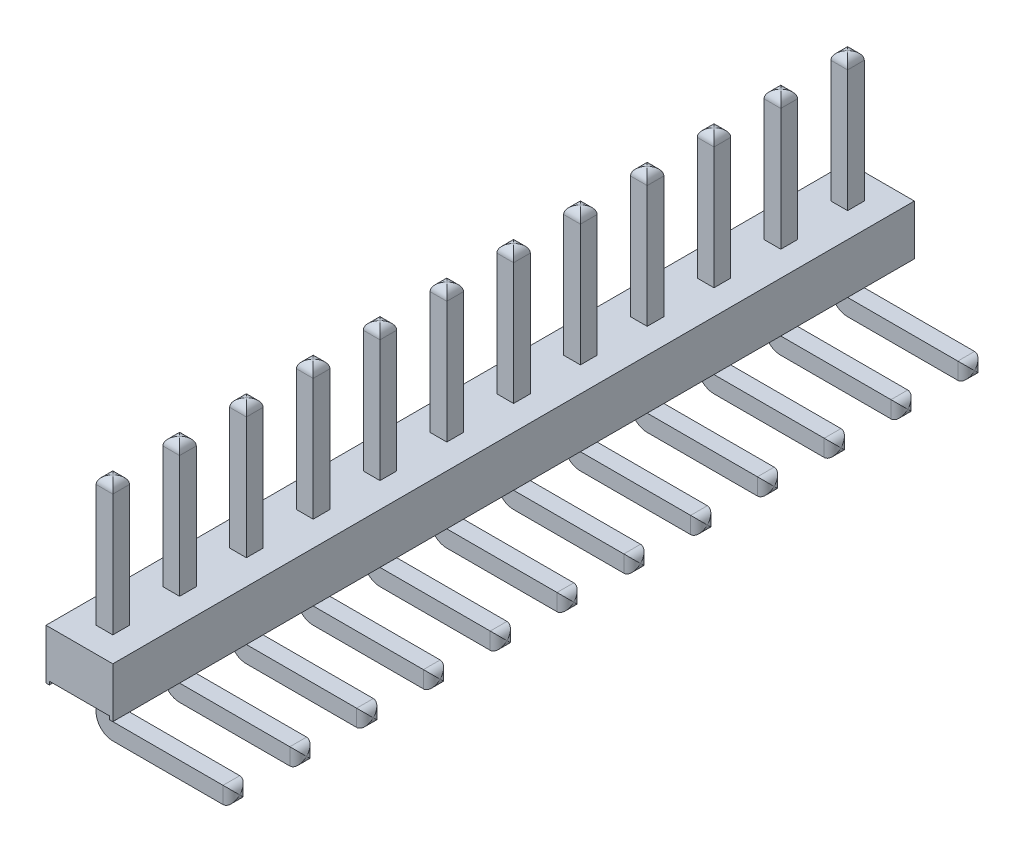
SolidWorks part; units mm, degrees
material "銅"
ref_plane "Front Plane" through (0, 0, 0) normal (0, 0, 1) x (1, 0, 0)
ref_plane "Top Plane" through (0, 0, 0) normal (0, 1, 0) x (1, 0, 0)
ref_plane "Right Plane" through (0, 0, 0) normal (1, 0, 0) x (0, 0, -1)
sketch "Sketch1" plane through (0, 0, 0) normal (0, 0, 1) x (1, 0, 0)
  line L0 (0.1, -1.5) -> (0.1, -1.3997)
  line L1 (0, 0) -> (2, 0)
  line L2 (0, 0) -> (0, -1.5)
  line L3 (0, -1.5) -> (0.1, -1.5)
  line L4 (2, 0) -> (2, -1.5)
  line L5 (0.1, -1.3997) -> (1.9019, -1.3997)
  line L6 (1.9019, -1.3997) -> (1.9019, -1.5)
  line L7 (1.9019, -1.5) -> (2, -1.5)
  dimension "D1" = 2
  dimension "D2" = 1.5
  dimension "D3" = 0.1
extrude "Boss-Extrude1" add sketch "Sketch1" against normal blind 24
sketch "Sketch2" plane through (0, 0, 0) normal (0, 1, 0) x (1, 0, 0)
  line L0 (1, 24) -> (1, 0) construction
  line L1 (2, 24) -> (0, 24) construction
  line L2 (2, 0) -> (0, 0) construction
  line L3 (1, 23.25) -> (0.75, 23.25)
  line L4 (0.75, 23.25) -> (0.75, 22.75)
  line L5 (0.75, 22.75) -> (1, 22.75)
  line L6 (1, 22.75) -> (1.25, 22.75)
  line L7 (1.25, 22.75) -> (1.25, 23.25)
  line L8 (1.25, 23.25) -> (1, 23.25)
  line L9 (0.75, 20.75) -> (1, 20.75)
  line L10 (0.75, 21.25) -> (0.75, 20.75)
  line L11 (1, 21.25) -> (0.75, 21.25)
  line L12 (1.25, 21.25) -> (1, 21.25)
  line L13 (1.25, 20.75) -> (1.25, 21.25)
  line L14 (1, 20.75) -> (1.25, 20.75)
  line L15 (0.75, 18.75) -> (1, 18.75)
  line L16 (0.75, 19.25) -> (0.75, 18.75)
  line L17 (1, 19.25) -> (0.75, 19.25)
  line L18 (1.25, 19.25) -> (1, 19.25)
  line L19 (1.25, 18.75) -> (1.25, 19.25)
  line L20 (1, 18.75) -> (1.25, 18.75)
  line L21 (0.75, 16.75) -> (1, 16.75)
  line L22 (0.75, 17.25) -> (0.75, 16.75)
  line L23 (1, 17.25) -> (0.75, 17.25)
  line L24 (1.25, 17.25) -> (1, 17.25)
  line L25 (1.25, 16.75) -> (1.25, 17.25)
  line L26 (1, 16.75) -> (1.25, 16.75)
  line L27 (0.75, 14.75) -> (1, 14.75)
  line L28 (0.75, 15.25) -> (0.75, 14.75)
  line L29 (1, 15.25) -> (0.75, 15.25)
  line L30 (1.25, 15.25) -> (1, 15.25)
  line L31 (1.25, 14.75) -> (1.25, 15.25)
  line L32 (1, 14.75) -> (1.25, 14.75)
  line L33 (0.75, 12.75) -> (1, 12.75)
  line L34 (0.75, 13.25) -> (0.75, 12.75)
  line L35 (1, 13.25) -> (0.75, 13.25)
  line L36 (1.25, 13.25) -> (1, 13.25)
  line L37 (1.25, 12.75) -> (1.25, 13.25)
  line L38 (1, 12.75) -> (1.25, 12.75)
  line L39 (0.75, 10.75) -> (1, 10.75)
  line L40 (0.75, 11.25) -> (0.75, 10.75)
  line L41 (1, 11.25) -> (0.75, 11.25)
  line L42 (1.25, 11.25) -> (1, 11.25)
  line L43 (1.25, 10.75) -> (1.25, 11.25)
  line L44 (1, 10.75) -> (1.25, 10.75)
  line L45 (0.75, 8.75) -> (1, 8.75)
  line L46 (0.75, 9.25) -> (0.75, 8.75)
  line L47 (1, 9.25) -> (0.75, 9.25)
  line L48 (1.25, 9.25) -> (1, 9.25)
  line L49 (1.25, 8.75) -> (1.25, 9.25)
  line L50 (1, 8.75) -> (1.25, 8.75)
  line L51 (0.75, 6.75) -> (1, 6.75)
  line L52 (0.75, 7.25) -> (0.75, 6.75)
  line L53 (1, 7.25) -> (0.75, 7.25)
  line L54 (1.25, 7.25) -> (1, 7.25)
  line L55 (1.25, 6.75) -> (1.25, 7.25)
  line L56 (1, 6.75) -> (1.25, 6.75)
  line L57 (0.75, 4.75) -> (1, 4.75)
  line L58 (0.75, 5.25) -> (0.75, 4.75)
  line L59 (1, 5.25) -> (0.75, 5.25)
  line L60 (1.25, 5.25) -> (1, 5.25)
  line L61 (1.25, 4.75) -> (1.25, 5.25)
  line L62 (1, 4.75) -> (1.25, 4.75)
  line L63 (0.75, 2.75) -> (1, 2.75)
  line L64 (0.75, 3.25) -> (0.75, 2.75)
  line L65 (1, 3.25) -> (0.75, 3.25)
  line L66 (1.25, 3.25) -> (1, 3.25)
  line L67 (1.25, 2.75) -> (1.25, 3.25)
  line L68 (1, 2.75) -> (1.25, 2.75)
  line L69 (0.75, 0.75) -> (1, 0.75)
  line L70 (0.75, 1.25) -> (0.75, 0.75)
  line L71 (1, 1.25) -> (0.75, 1.25)
  line L72 (1.25, 1.25) -> (1, 1.25)
  line L73 (1.25, 0.75) -> (1.25, 1.25)
  line L74 (1, 0.75) -> (1.25, 0.75)
  dimension "D1" = 0.25
  dimension "D2" = 0.25
  dimension "D3" = 0.5
  dimension "D4" = 12
extrude "Boss-Extrude2" add sketch "Sketch2" along normal blind 3.9
fillet "Fillet1" radius 0.25 48 edges at (1.25, 3.9, -11) (1, 3.9, -10.75) (0.75, 3.9, -11) (1, 3.9, -11.25) (1.25, 3.9, -9) (1, 3.9, -8.75) (0.75, 3.9, -9) (1, 3.9, -9.25) (1.25, 3.9, -7) (1, 3.9, -6.75) (0.75, 3.9, -7) (1, 3.9, -7.25) (1.25, 3.9, -5) (1, 3.9, -4.75) (0.75, 3.9, -5) (1, 3.9, -5.25) (1.25, 3.9, -3) (1, 3.9, -2.75) (0.75, 3.9, -3) (1, 3.9, -3.25) (1.25, 3.9, -1) (1, 3.9, -0.75) (0.75, 3.9, -1) (1, 3.9, -1.25) (1.25, 3.9, -13) (1, 3.9, -12.75) (0.75, 3.9, -13) (1, 3.9, -13.25) (1.25, 3.9, -15) (1, 3.9, -14.75) (0.75, 3.9, -15) (1, 3.9, -15.25) (1.25, 3.9, -17) (1, 3.9, -16.75) (0.75, 3.9, -17) (1, 3.9, -17.25) (1.25, 3.9, -19) (1, 3.9, -18.75) (0.75, 3.9, -19) (1, 3.9, -19.25) (1.25, 3.9, -21) (1, 3.9, -20.75) (0.75, 3.9, -21) (1, 3.9, -21.25) (1.25, 3.9, -23) (1, 3.9, -22.75) (0.75, 3.9, -23) (1, 3.9, -23.25)
sketch "Sketch3" plane through (0, -1.3997, 0) normal (0, -1, 0) x (-1, 0, 0)
  line L0 (-1.2509, 20.7494) -> (-0.7509, 20.7494)
  line L1 (-1.2509, 23.2506) -> (-0.7509, 23.2506)
  line L2 (-1.2509, 23.2506) -> (-1.2509, 22.7494)
  line L3 (-1.2509, 22.7494) -> (-0.7509, 22.7494)
  line L4 (-0.7509, 23.2506) -> (-0.7509, 22.7494)
  line L5 (-0.1, 24) -> (-1.9019, 24) construction
  line L6 (-1.0009, 24) -> (-1.0009, 0) construction
  line L7 (-0.1, 0) -> (-1.9019, 0) construction
  line L8 (-0.7509, 21.2506) -> (-0.7509, 20.7494)
  line L9 (-1.2509, 21.2506) -> (-0.7509, 21.2506)
  line L10 (-1.2509, 21.2506) -> (-1.2509, 20.7494)
  line L11 (-1.2509, 18.7494) -> (-0.7509, 18.7494)
  line L12 (-0.7509, 19.2506) -> (-0.7509, 18.7494)
  line L13 (-1.2509, 19.2506) -> (-0.7509, 19.2506)
  line L14 (-1.2509, 19.2506) -> (-1.2509, 18.7494)
  line L15 (-1.2509, 16.7494) -> (-0.7509, 16.7494)
  line L16 (-0.7509, 17.2506) -> (-0.7509, 16.7494)
  line L17 (-1.2509, 17.2506) -> (-0.7509, 17.2506)
  line L18 (-1.2509, 17.2506) -> (-1.2509, 16.7494)
  line L19 (-1.2509, 14.7494) -> (-0.7509, 14.7494)
  line L20 (-0.7509, 15.2506) -> (-0.7509, 14.7494)
  line L21 (-1.2509, 15.2506) -> (-0.7509, 15.2506)
  line L22 (-1.2509, 15.2506) -> (-1.2509, 14.7494)
  line L23 (-1.2509, 12.7494) -> (-0.7509, 12.7494)
  line L24 (-0.7509, 13.2506) -> (-0.7509, 12.7494)
  line L25 (-1.2509, 13.2506) -> (-0.7509, 13.2506)
  line L26 (-1.2509, 13.2506) -> (-1.2509, 12.7494)
  line L27 (-1.2509, 10.7494) -> (-0.7509, 10.7494)
  line L28 (-0.7509, 11.2506) -> (-0.7509, 10.7494)
  line L29 (-1.2509, 11.2506) -> (-0.7509, 11.2506)
  line L30 (-1.2509, 11.2506) -> (-1.2509, 10.7494)
  line L31 (-1.2509, 8.7494) -> (-0.7509, 8.7494)
  line L32 (-0.7509, 9.2506) -> (-0.7509, 8.7494)
  line L33 (-1.2509, 9.2506) -> (-0.7509, 9.2506)
  line L34 (-1.2509, 9.2506) -> (-1.2509, 8.7494)
  line L35 (-1.2509, 6.7494) -> (-0.7509, 6.7494)
  line L36 (-0.7509, 7.2506) -> (-0.7509, 6.7494)
  line L37 (-1.2509, 7.2506) -> (-0.7509, 7.2506)
  line L38 (-1.2509, 7.2506) -> (-1.2509, 6.7494)
  line L39 (-1.2509, 4.7494) -> (-0.7509, 4.7494)
  line L40 (-0.7509, 5.2506) -> (-0.7509, 4.7494)
  line L41 (-1.2509, 5.2506) -> (-0.7509, 5.2506)
  line L42 (-1.2509, 5.2506) -> (-1.2509, 4.7494)
  line L43 (-1.2509, 2.7494) -> (-0.7509, 2.7494)
  line L44 (-0.7509, 3.2506) -> (-0.7509, 2.7494)
  line L45 (-1.2509, 3.2506) -> (-0.7509, 3.2506)
  line L46 (-1.2509, 3.2506) -> (-1.2509, 2.7494)
  line L47 (-1.2509, 0.7494) -> (-0.7509, 0.7494)
  line L48 (-0.7509, 1.2506) -> (-0.7509, 0.7494)
  line L49 (-1.2509, 1.2506) -> (-0.7509, 1.2506)
  line L50 (-1.2509, 1.2506) -> (-1.2509, 0.7494)
  dimension "D1" = 12
  dimension "D2" = 0.25
  dimension "D3" = 0.25
extrude "Boss-Extrude3" add sketch "Sketch3" along normal blind 1.35
sketch "Sketch5" plane through (1.2509, 0, 0) normal (1, 0, 0) x (0, 0, -1)
  line L0 (1.2506, -2.7497) -> (1.2506, -1.3997) construction
  line L1 (0.7494, -2.7497) -> (1.2506, -2.7497)
  line L2 (0.7494, -2.7497) -> (0.7494, -2.2497)
  line L3 (0.7494, -2.2497) -> (1.2506, -2.2497)
  line L4 (1.2506, -2.7497) -> (1.2506, -2.2497)
  line L5 (2.7494, -2.2497) -> (3.2506, -2.2497)
  line L6 (2.7494, -2.7497) -> (2.7494, -2.2497)
  line L7 (3.2506, -2.7497) -> (3.2506, -2.2497)
  line L8 (2.7494, -2.7497) -> (3.2506, -2.7497)
  line L9 (4.7494, -2.2497) -> (5.2506, -2.2497)
  line L10 (4.7494, -2.7497) -> (4.7494, -2.2497)
  line L11 (5.2506, -2.7497) -> (5.2506, -2.2497)
  line L12 (4.7494, -2.7497) -> (5.2506, -2.7497)
  line L13 (6.7494, -2.2497) -> (7.2506, -2.2497)
  line L14 (6.7494, -2.7497) -> (6.7494, -2.2497)
  line L15 (7.2506, -2.7497) -> (7.2506, -2.2497)
  line L16 (6.7494, -2.7497) -> (7.2506, -2.7497)
  line L17 (8.7494, -2.2497) -> (9.2506, -2.2497)
  line L18 (8.7494, -2.7497) -> (8.7494, -2.2497)
  line L19 (9.2506, -2.7497) -> (9.2506, -2.2497)
  line L20 (8.7494, -2.7497) -> (9.2506, -2.7497)
  line L21 (10.7494, -2.2497) -> (11.2506, -2.2497)
  line L22 (10.7494, -2.7497) -> (10.7494, -2.2497)
  line L23 (11.2506, -2.7497) -> (11.2506, -2.2497)
  line L24 (10.7494, -2.7497) -> (11.2506, -2.7497)
  line L25 (12.7494, -2.2497) -> (13.2506, -2.2497)
  line L26 (12.7494, -2.7497) -> (12.7494, -2.2497)
  line L27 (13.2506, -2.7497) -> (13.2506, -2.2497)
  line L28 (12.7494, -2.7497) -> (13.2506, -2.7497)
  line L29 (14.7494, -2.2497) -> (15.2506, -2.2497)
  line L30 (14.7494, -2.7497) -> (14.7494, -2.2497)
  line L31 (15.2506, -2.7497) -> (15.2506, -2.2497)
  line L32 (14.7494, -2.7497) -> (15.2506, -2.7497)
  line L33 (16.7494, -2.2497) -> (17.2506, -2.2497)
  line L34 (16.7494, -2.7497) -> (16.7494, -2.2497)
  line L35 (17.2506, -2.7497) -> (17.2506, -2.2497)
  line L36 (16.7494, -2.7497) -> (17.2506, -2.7497)
  line L37 (18.7494, -2.2497) -> (19.2506, -2.2497)
  line L38 (18.7494, -2.7497) -> (18.7494, -2.2497)
  line L39 (19.2506, -2.7497) -> (19.2506, -2.2497)
  line L40 (18.7494, -2.7497) -> (19.2506, -2.7497)
  line L41 (20.7494, -2.2497) -> (21.2506, -2.2497)
  line L42 (20.7494, -2.7497) -> (20.7494, -2.2497)
  line L43 (21.2506, -2.7497) -> (21.2506, -2.2497)
  line L44 (20.7494, -2.7497) -> (21.2506, -2.7497)
  line L45 (22.7494, -2.2497) -> (23.2506, -2.2497)
  line L46 (22.7494, -2.7497) -> (22.7494, -2.2497)
  line L47 (23.2506, -2.7497) -> (23.2506, -2.2497)
  line L48 (22.7494, -2.7497) -> (23.2506, -2.7497)
  dimension "D1" = 0.5
  dimension "D2" = 12
extrude "Boss-Extrude5" add sketch "Sketch5" along normal blind 3.55
fillet "Fillet4" radius 0.25 48 edges at (4.8009, -2.4997, -10.7494) (4.8009, -2.2497, -11) (4.8009, -2.4997, -11.2506) (4.8009, -2.7497, -11) (4.8009, -2.4997, -12.7494) (4.8009, -2.2497, -13) (4.8009, -2.4997, -13.2506) (4.8009, -2.7497, -13) (4.8009, -2.4997, -14.7494) (4.8009, -2.2497, -15) (4.8009, -2.4997, -15.2506) (4.8009, -2.7497, -15) (4.8009, -2.4997, -16.7494) (4.8009, -2.2497, -17) (4.8009, -2.4997, -17.2506) (4.8009, -2.7497, -17) (4.8009, -2.4997, -18.7494) (4.8009, -2.2497, -19) (4.8009, -2.4997, -19.2506) (4.8009, -2.7497, -19) (4.8009, -2.4997, -20.7494) (4.8009, -2.2497, -21) (4.8009, -2.4997, -21.2506) (4.8009, -2.7497, -21) (4.8009, -2.4997, -22.7494) (4.8009, -2.2497, -23) (4.8009, -2.4997, -23.2506) (4.8009, -2.7497, -23) (4.8009, -2.4997, -8.7494) (4.8009, -2.2497, -9) (4.8009, -2.4997, -9.2506) (4.8009, -2.7497, -9) (4.8009, -2.4997, -6.7494) (4.8009, -2.2497, -7) (4.8009, -2.4997, -7.2506) (4.8009, -2.7497, -7) (4.8009, -2.4997, -4.7494) (4.8009, -2.2497, -5) (4.8009, -2.4997, -5.2506) (4.8009, -2.7497, -5) (4.8009, -2.4997, -2.7494) (4.8009, -2.2497, -3) (4.8009, -2.4997, -3.2506) (4.8009, -2.7497, -3) (4.8009, -2.2497, -1) (4.8009, -2.4997, -1.2506) (4.8009, -2.7497, -1) (4.8009, -2.4997, -0.7494)
fillet "Fillet5" radius 0.5 12 edges at (0.7509, -2.7497, -1) (0.7509, -2.7497, -3) (0.7509, -2.7497, -5) (0.7509, -2.7497, -7) (0.7509, -2.7497, -9) (0.7509, -2.7497, -11) (0.7509, -2.7497, -13) (0.7509, -2.7497, -15) (0.7509, -2.7497, -17) (0.7509, -2.7497, -19) (0.7509, -2.7497, -21) (0.7509, -2.7497, -23)
